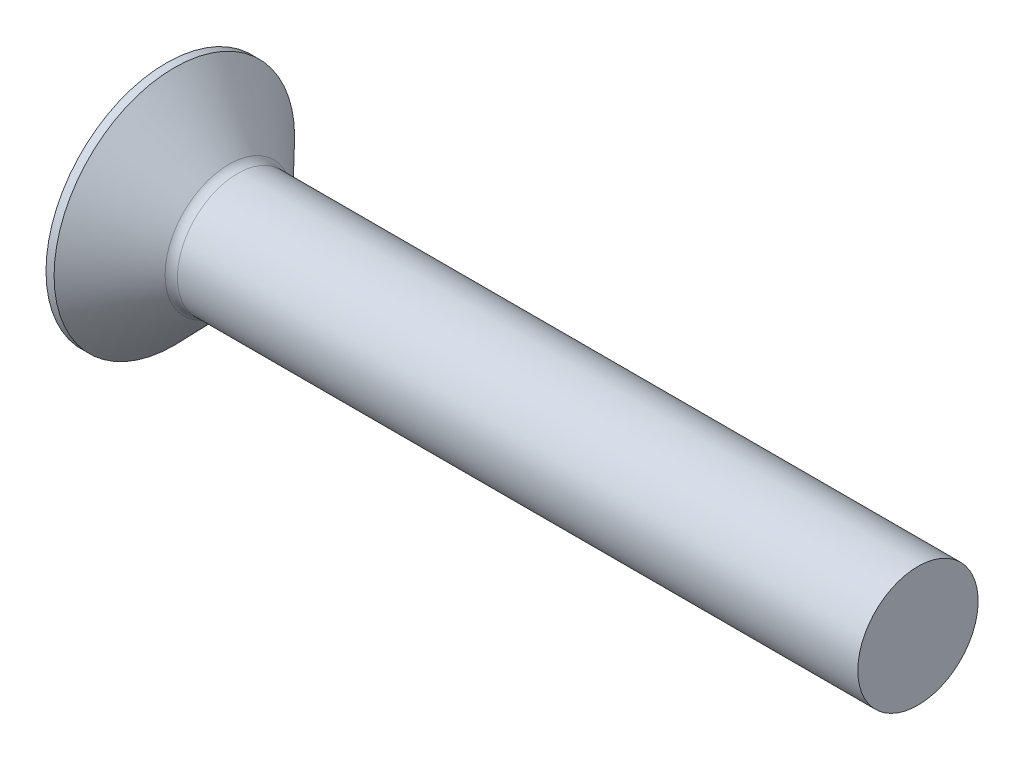
SolidWorks part; units mm, degrees
ref_plane "Front Plane" through (0, 0, 0) normal (0, 0, 1) x (1, 0, 0)
ref_plane "Top Plane" through (0, 0, 0) normal (0, 1, 0) x (1, 0, 0)
ref_plane "Right Plane" through (0, 0, 0) normal (1, 0, 0) x (0, 0, -1)
sketch "BodySke" plane through (0, 0, 0) normal (0, 0, 1) x (1, 0, 0)
  line L0 (1.8, 0) -> (111.3824, 0) construction
  line L1 (1.8, 0) -> (1.8, 8) construction
  line L2 (1.8, 8) -> (2.3372, 8)
  line L3 (2.3372, 8) -> (6.2, 4)
  line L4 (6.2, 4) -> (51.8, 4)
  line L5 (51.8, 4) -> (51.8, 0)
  line L6 (7.45, 1.8551) -> (7.45, -12.8628) construction
  line L7 (1.8, 0) -> (51.8, 0)
  line L8 (21.8, 2.8551) -> (21.8, -10.9269) construction
  line L9 (1.8, -8) -> (2.3372, -8) construction
  line L10 (2.3372, -8) -> (6.2, -4) construction
  line L11 (6.2, -4) -> (51.8, -4) construction
  line L12 (1.8, 0) -> (-7.747, 0) construction
  line L13 (0, 0) -> (0, 16.1338) construction
  line L14 (1.8, 0) -> (0, 0)
  arc A0 (0, 0) -> (1.8, 8) centre (18.6778, 0) cw
  point P10 (51.8, 3.4455)
  dimension "Thread_minor" = 6.891
  dimension "Length" = 50
  dimension "Head_height" = 4.4
  dimension "Head_dia" = 16
  dimension "Advance" = 1.25
revolve "BaseBody" add sketch "BodySke" angle 360 about L0
cosmetic thread "ThreadCosmetic" [suppressed] parameters "Thread_minor"=6.891
fillet "Fillet1" radius 0.8 1 edges at (6.2, 0, 4)
ref_plane "Plane1" through (5.18, 0, 0) normal (1, 0, 0) x (0, 0, -1)
sketch "RecSkeTop" plane through (0, 0, 0) normal (1, 0, 0) x (0, 0, -1)
  line L1 (-0.946, 4.3) -> (0.946, 4.3)
  line L2 (-0.946, 4.3) -> (-0.946, -4.3)
  line L3 (-0.946, -4.3) -> (0.946, -4.3)
  line L4 (0.946, 4.3) -> (0.946, -4.3)
  dimension "D1" = 4.3
  dimension "D2" = 1.892
  dimension "D3" = 0.946
sketch "RecSkeBot" plane through (5.18, 0, 0) normal (1, 0, 0) x (0, 0, -1)
  line L0 (-0.946, 4.3) -> (-0.946, -4.3) construction
  line L1 (-0.946, 1.7173) -> (0.946, 1.7173)
  line L2 (-0.946, 1.7173) -> (-0.946, -1.7173)
  line L3 (-0.946, -1.7173) -> (0.946, -1.7173)
  line L4 (0.946, 1.7173) -> (0.946, -1.7173)
  line L5 (0.946, 4.3) -> (0.946, -4.3) construction
  dimension "D1" = 3.4347
  dimension "D2" = 1.7173
loft "Recess" cut profiles "RecSkeTop", "RecSkeBot" connector at (0, -4.3, 0.946) connector at (5.18, -1.7173, 0.946)
pattern_circular "RecPat" count 2 every 90 about axis through (1.8, 0, 0) along (1, 0, 0) of "Recess"
sketch "RecCorSke" plane through (0, 0, 0) normal (0, 0, 1) x (1, 0, 0)
  line L0 (0, 0) -> (57.5987, 0) construction
  line L1 (0, 0) -> (0, 2.0812)
  line L3 (0, 2.0812) -> (5.18, 1.719)
  line L4 (5.18, 1.719) -> (5.7385, 0)
  line L5 (5.7385, 0) -> (0, 0)
  dimension "D1" = 18
  dimension "D2" = 5.18
  dimension "D3" = 2.0812
  dimension "D4" = 4
revolve "RecessCore" cut sketch "RecCorSke" angle 360 about L0
sketch "ThdSchSke" plane through (0, 0, 0) normal (0, 0, 1) x (1, 0, 0)
  line L0 (0, 0) -> (55.1256, 0) construction
  line L1 (1.8, 0) -> (111.3824, 0) construction
  line L2 (51.4799, 4) -> (51.4799, 4.6403)
  line L3 (51.4799, 4.6403) -> (52.1201, 4.6403)
  line L4 (52.1201, 4.6403) -> (52.1201, 4)
  line L5 (52.1201, 4) -> (51.8, 3.4455)
  line L6 (51.8, 3.4455) -> (51.4799, 4)
  line L7 (6.2, 4) -> (51.8, 4) construction
  line L13 (51.8, 4) -> (51.8, 0) construction
revolve "ThreadSchematic" [suppressed] cut sketch "ThdSchSke" angle 360 about L0
pattern_linear "ThdSchPat" [suppressed] count 24 along (-1, 0, 0) of bodies 103
equation "\"Thread_minor@ThreadCosmetic\" = \"Thread_minor@BodySke\""
equation "\"D1@RecSkeTop\" = \"Cross_dia@RecSkeTop\" / 2"
equation "\"D2@RecSkeTop\" = \"Cross_dia@RecSkeTop\" * 0.22"
equation "\"D3@RecSkeTop\" = \"D2@RecSkeTop\" / 2"
equation "\"D1@RecSkeBot\" = \"Cross_dia@RecSkeTop\" - 2 * \"Cross_depth@Plane1\" *  tan( 26.5 * 0.017453292 ) "
equation "\"D2@RecSkeBot\" = \"D1@RecSkeBot\" / 2"
equation "\"D2@RecCorSke\" = \"Cross_depth@Plane1\""
equation "\"D3@RecCorSke\" = \"D2@RecSkeTop\" * 1.1"
equation "\"Advance@ThdSchPat\" = \"Advance@BodySke\""
equation "\"D1@ThdSchPat\" =  int( \"Thread_length@BodySke\" / \"Advance@ThdSchPat\" ) "
